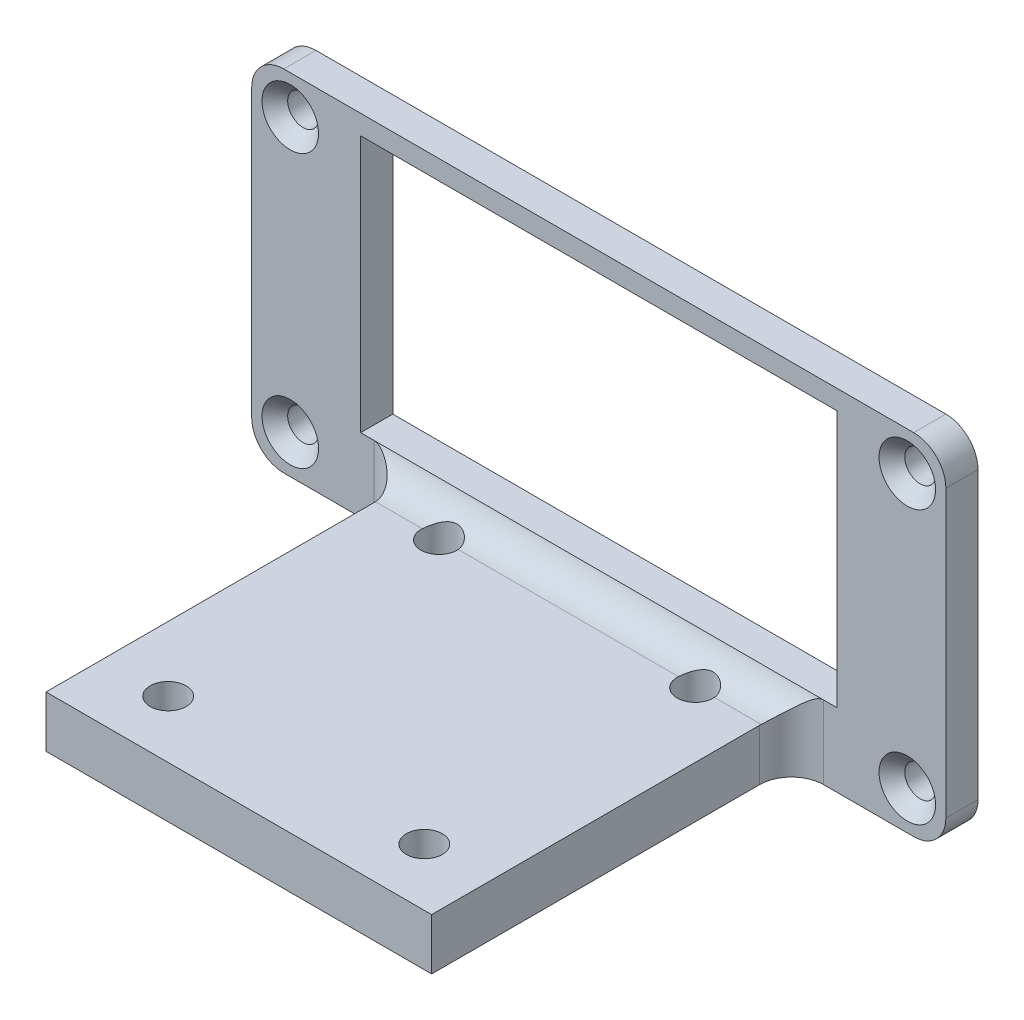
SolidWorks part; units mm, degrees
ref_plane "Front Plane" through (0, 0, 0) normal (0, 0, 1) x (1, 0, 0)
ref_plane "Top Plane" through (0, 0, 0) normal (0, 1, 0) x (1, 0, 0)
ref_plane "Right Plane" through (0, 0, 0) normal (1, 0, 0) x (0, 0, -1)
sketch "Sketch1" plane through (0, 0, 0) normal (0, 0, 1) x (1, 0, 0)
  line L1 (18.525, -10) -> (-18.525, -10)
  line L2 (18.525, -10) -> (18.525, 10)
  line L3 (18.525, 10) -> (-18.525, 10)
  line L4 (-18.525, -10) -> (-18.525, 10)
  line L5 (18.525, -10) -> (-18.525, 10) construction
  line L6 (18.525, 10) -> (-18.525, -10) construction
  line L7 (27, 11.515) -> (-27, 11.515)
  line L8 (27, 11.515) -> (27, -15.705)
  line L9 (27, -15.705) -> (-27, -15.705)
  line L10 (-27, 11.515) -> (-27, -15.705)
  line L12 (0, 11.515) -> (0, -15.705) construction
  point P0 (0, 0)
  dimension "D1" = 37.05
  dimension "D2" = 20
  dimension "D3" = 54
  dimension "D4" = 27.22
  dimension "D5" = 15.705
extrude "Boss-Extrude1" add sketch "Sketch1" along normal blind 2.5
hole_wizard "CSK for M2 Flat Head Machine Screw1" positions "Sketch6" profile "Sketch7" countersink size "M2" standard "ANSI Metric" end condition through all
sketch "Sketch6" plane through (0, 0, 2.5) normal (0, 0, 1) x (1, 0, 0)
  line L0 (27, 11.515) -> (-27, 11.515) construction
  line L1 (-27, 11.515) -> (-27, -15.705) construction
  line L2 (-27, -15.705) -> (27, -15.705) construction
  line L3 (27, -15.705) -> (27, 11.515) construction
  point P0 (-24, 8.515)
  point P2 (-24, -12.705)
  point P4 (24, 8.515)
  point P6 (24, -12.705)
  dimension "D1" = 3
  dimension "D2" = 3
  dimension "D3" = 3
  dimension "D4" = 3
  dimension "D5" = 3
  dimension "D6" = 3
  dimension "D7" = 3
  dimension "D8" = 3
sketch "Sketch7" plane through (-24, 8.515, 2.5) normal (1, 0, 0) x (0, -1, 0)
  line L0 (0, 0) -> (0, 2.5)
  line L1 (0, 2.5) -> (1.2, 2.5)
  line L2 (1.2, 2.5) -> (1.2, 1)
  line L3 (1.2, 1) -> (2.2, 0)
  line L5 (2.2, 0) -> (0, 0)
  line L6 (-1.2, 1) -> (-2.2, 0) construction
  line L11 (0, -6.35) -> (0, 107.95) construction
  dimension "Thru Hole Dia." = 2.4
  dimension "Thru Hole Depth" = 2.5
  dimension "Near C'Sink Dia." = 4.4
  dimension "Near C'Sink Angle" = 90
fillet "Fillet1" radius 2.5 4 edges at (-27, 11.515, 1.25) (-27, -15.705, 1.25) (27, -15.705, 1.25) (27, 11.515, 1.25)
sketch "Sketch8" plane through (0, -15.705, 0) normal (0, -1, 0) x (1, 0, 0)
  line L0 (0, 0) -> (0, 33) construction
  line L2 (-15, 30.5) -> (15, 30.5)
  line L3 (-15, 30.5) -> (-15, 2.5)
  line L4 (-15, 2.5) -> (15, 2.5)
  line L5 (15, 30.5) -> (15, 2.5)
  line L6 (-15, 30.5) -> (15, 2.5) construction
  line L7 (-15, 2.5) -> (15, 30.5) construction
  line L11 (-24.5, 2.5) -> (24.5, 2.5) construction
  point P2 (0, 16.5)
  point P9 (21.02, 30.9442)
  point P10 (21.02, 32.8409)
  point P11 (0, 15.8468)
  dimension "D1" = 30
  dimension "D2" = 28
extrude "Boss-Extrude2" add sketch "Sketch8" against normal blind 4
fillet "Fillet2" radius 2.5 1 edges at (0, -11.705, 2.5)
fillet "Fillet3" radius 2.5 2 edges at (-15, -12.8525, 2.5) (15, -12.8525, 2.5)
hole_wizard "Ø2.8 (2.8) Diameter Hole1" positions "Sketch11" profile "Sketch10" hole size "Ø2.8" standard "ANSI Metric" end condition through all
sketch "Sketch11" plane through (0, -15.705, 0) normal (0, -1, 0) x (-1, 0, 0)
  point P0 (-9.9638, -4.9672)
  point P3 (9.9638, -4.9672)
  point P6 (9.9638, -26.0328)
  point P9 (-9.9638, -26.0328)
sketch "Sketch10" plane through (9.9638, -15.705, 4.9672) normal (1, 0, 0) x (0, 0, -1)
  line L0 (0, 0) -> (0, 27.22)
  line L1 (0, 27.22) -> (1.4, 27.22)
  line L2 (1.4, 27.22) -> (1.4, 0)
  line L5 (1.4, 0) -> (0, 0)
  line L11 (0, -6.35) -> (0, 107.95) construction
  dimension "Thru Hole Dia." = 2.8
  dimension "Thru Hole Depth" = 27.22
